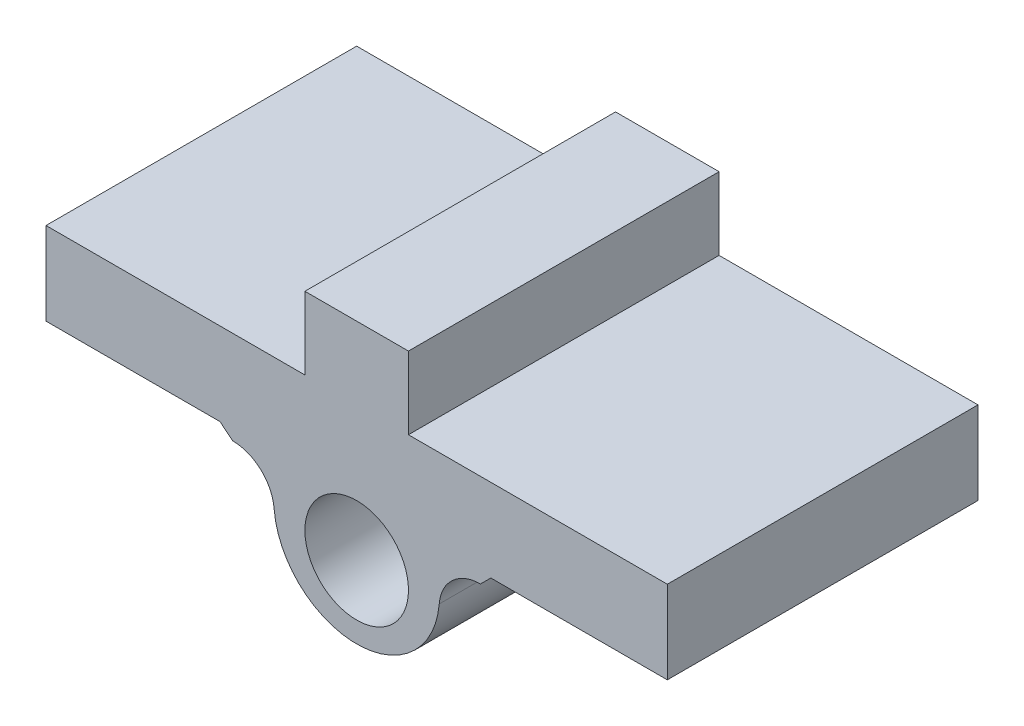
SolidWorks part; units mm, degrees
ref_plane "Front Plane" through (0, 0, 0) normal (0, 0, 1) x (1, 0, 0)
ref_plane "Top Plane" through (0, 0, 0) normal (0, 1, 0) x (1, 0, 0)
ref_plane "Right Plane" through (0, 0, 0) normal (1, 0, 0) x (0, 0, -1)
sketch "Sketch1" plane through (0, 0, 0) normal (0, 1, 0) x (1, 0, 0)
  line L1 (0, 0) -> (60, 0)
  line L2 (0, 0) -> (0, 30)
  line L3 (0, 30) -> (60, 30)
  line L4 (60, 0) -> (60, 30)
  dimension "D1" = 30
  dimension "D2" = 60
extrude "Boss-Extrude1" add sketch "Sketch1" along normal blind 8
sketch "Sketch3" plane through (0, 8, 0) normal (0, 1, 0) x (1, 0, 0)
  line L0 (60, 30) -> (0, 30) construction
  line L1 (25, 30) -> (35, 30)
  line L2 (25, 30) -> (25, 0)
  line L3 (25, 0) -> (35, 0)
  line L4 (35, 30) -> (35, 0)
  line L5 (0, 0) -> (60, 0) construction
  line L6 (0, 30) -> (0, 0) construction
  dimension "D1" = 10
  dimension "D2" = 25
extrude "Boss-Extrude5" add sketch "Sketch3" along normal blind 7
sketch "Sketch5" plane through (0, 0, 0) normal (0, -1, 0) x (1, 0, 0)
  line L0 (0, 0) -> (60, 0) construction
  line L1 (23, 0) -> (37, 0)
  line L2 (23, 0) -> (23, -30)
  line L3 (23, -30) -> (37, -30)
  line L4 (37, 0) -> (37, -30)
  line L5 (60, -30) -> (0, -30) construction
  line L6 (0, -30) -> (0, 0) construction
  dimension "D1" = 14
  dimension "D2" = 23
extrude "Boss-Extrude6" add sketch "Sketch5" along normal blind 11
sketch "Sketch6" plane through (0, 0, -30) normal (0, 0, -1) x (-1, 0, 0)
  line L0 (-23, -11) -> (-23, 0) construction
  line L1 (-37, -11) -> (-37, 0) construction
  line L2 (-23, -11) -> (-37, -11) construction
  circle A0 centre (-30, -5) radius 5
  dimension "D1" = 7
  dimension "D2" = 14
  dimension "D3" = 6
extrude "Cut-Extrude1" cut sketch "Sketch6" against normal through all
fillet "Fillet1" radius 7 2 edges at (23, -11, -15) (37, -11, -15)
fillet "Fillet2" radius 5 1 edges at (23, 0, -15)
fillet "Fillet3" radius 5 1 edges at (37, 0, -15)
sketch "Sketch8" plane through (0, 0, -30) normal (0, 0, -1) x (-1, 0, 0)
  line L0 (-41.9583, -1) -> (-42.9583, 0)
  line L1 (-60, 0) -> (-41.9583, 0) construction
  line L2 (-42.9583, 0) -> (-41.9583, 0)
  line L3 (-18.0417, -1) -> (-16.803, 0)
  line L4 (-18.0417, 0) -> (0, 0) construction
  line L5 (-16.803, 0) -> (-18.0417, 0)
  arc A0 (-18.0417, 0) -> (-23.0243, -4.5833) centre (-18.0417, -5) ccw construction
  arc A1 (-30, -11) -> (-23.0243, -4.5833) centre (-30, -4) ccw construction
  arc A2 (-36.9757, -4.5833) -> (-30, -11) centre (-30, -4) ccw construction
  arc A3 (-36.9757, -4.5833) -> (-41.9583, 0) centre (-41.9583, -5) ccw construction
  arc A4 (-18.0417, 0) -> (-23.0243, -4.5833) centre (-18.0417, -5) ccw
  arc A5 (-30, -11) -> (-23.0243, -4.5833) centre (-30, -4) ccw
  arc A6 (-36.9757, -4.5833) -> (-30, -11) centre (-30, -4) ccw
  arc A7 (-36.9757, -4.5833) -> (-41.9583, 0) centre (-41.9583, -5) ccw
  arc A8 (-18.0417, -1) -> (-22.0278, -4.6667) centre (-18.0417, -5) ccw
  arc A9 (-30, -12) -> (-22.0278, -4.6667) centre (-30, -4) ccw
  arc A10 (-37.9722, -4.6667) -> (-30, -12) centre (-30, -4) ccw
  arc A11 (-37.9722, -4.6667) -> (-41.9583, -1) centre (-41.9583, -5) ccw
  dimension "D1" = 1
extrude "Boss-Extrude7" add sketch "Sketch8" against normal up to surface (30 mm away) up to face at (25, -5, 0)
